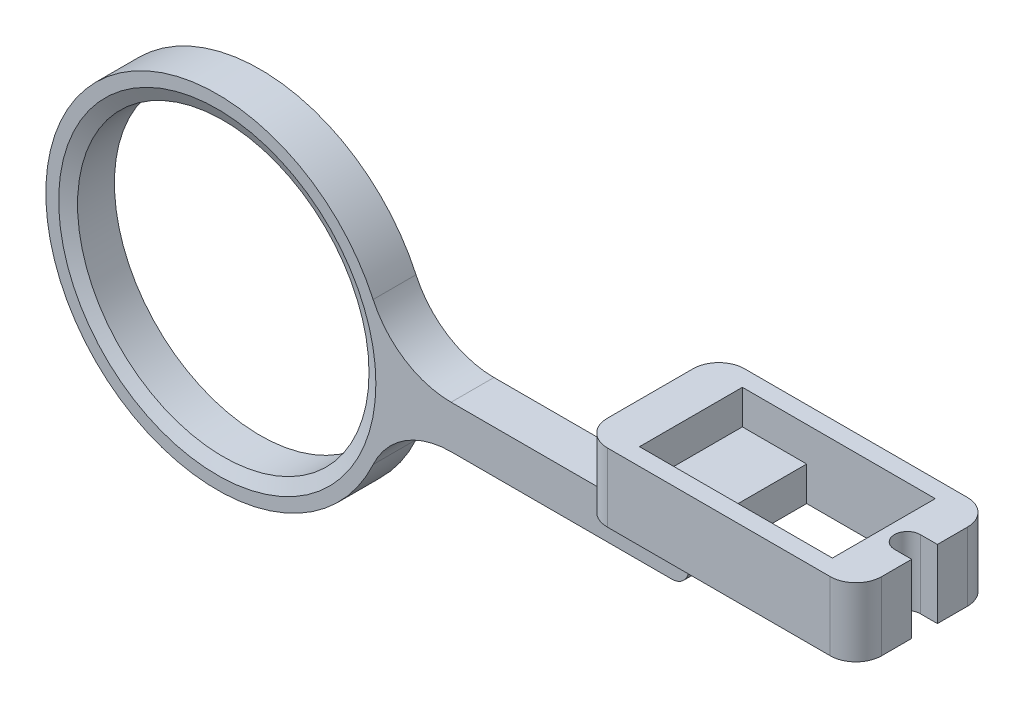
SolidWorks part; units mm, degrees
ref_plane "Plan de face" through (0, 0, 0) normal (0, 0, 1) x (1, 0, 0)
ref_plane "Plan de dessus" through (0, 0, 0) normal (0, 1, 0) x (1, 0, 0)
ref_plane "Plan de droite" through (0, 0, 0) normal (1, 0, 0) x (0, 0, -1)
sketch "Sketch1" plane through (0, 0, 0) normal (0, 0, 1) x (1, 0, 0)
  line L1 (0, 2.5) -> (80, 2.5)
  line L2 (0, 2.5) -> (0, -2.5)
  line L3 (0, -2.5) -> (80, -2.5)
  line L4 (80, 2.5) -> (80, -2.5)
  circle A0 centre (0, 0) radius 20
  circle A1 centre (0, 0) radius 17
  point P9 (0, 0)
  dimension "D1" = 40
  dimension "D3" = 80
  dimension "D4" = 5
  dimension "D2" = 3
extrude "Boss-Extrude1" add sketch "Sketch1" along normal blind 5 contours A1 L1 A0 L3 | A1 L3 A0 L1 | A0 L3 L4 L1 region at (-17.5646, 0, 0) region at (18.443, 0, 0) region at (49.9739, 0, 0)
chamfer "Chamfer2" distance 1.5 angle 25 1 edges at (17, 0, 5) first distance on face at (39.9608, 0, 5)
fillet "Fillet1" radius 10 2 edges at (19.8431, -2.5, 2.5) (19.8431, 2.5, 2.5)
sketch "Sketch4" plane through (0, 0, 0) normal (0, 1, 0) x (1, 0, 0)
  line L0 (18.5, -5) -> (17, -4.3005) construction
  circle A0 centre (0.2012, -29.5685) radius 30 construction
  dimension "D1" = 60
sketch "Sketch10" plane through (0, 2.5, 0) normal (0, 1, 0) x (1, 0, 0)
  line L0 (27.2718, 0) -> (80, 0) construction
  line L1 (80, -5) -> (48, -5)
  line L2 (80, -5) -> (80, 0)
  line L3 (80, 0) -> (48, 0)
  line L4 (48, -5) -> (48, 0)
  dimension "D1" = 32
extrude "Boss-Extrude3" add sketch "Sketch10" along normal blind 2
sketch "Sketch5" plane through (0, 4.5, 0) normal (0, 1, 0) x (1, 0, 0)
  line L0 (80, -5) -> (80, 0) construction
  line L1 (80, -10.5) -> (48, -10.5)
  line L2 (80, -10.5) -> (80, 5.5)
  line L3 (80, 5.5) -> (48, 5.5)
  line L4 (48, -10.5) -> (48, 5.5)
  point P7 (80, -2.5)
  point P8 (80, -2.5)
  dimension "D1" = 16
  dimension "D2" = 32
extrude "Boss-Extrude2" add sketch "Sketch5" along normal blind 8
sketch "Sketch6" plane through (0, 12.5, 0) normal (0, 1, 0) x (1, 0, 0)
  line L0 (80, 5.5) -> (48, 5.5) construction
  line L1 (52.75, 3.5) -> (75.25, 3.5)
  line L2 (52.75, 3.5) -> (52.75, -8.5)
  line L3 (52.75, -8.5) -> (75.25, -8.5)
  line L4 (75.25, 3.5) -> (75.25, -8.5)
  line L5 (80, -10.5) -> (80, 5.5) construction
  point P6 (64, 5.5)
  point P7 (64, 3.5)
  point P10 (80, -2.5)
  point P11 (75.25, -2.5)
  dimension "D1" = 12
  dimension "D2" = 22.5
extrude "Cut-Extrude1" cut sketch "Sketch6" against normal blind 4
sketch "Sketch7" plane through (0, -2.5, 0) normal (0, -1, 0) x (1, 0, 0)
  line L0 (27.2718, 0) -> (80, 0) construction
  line L1 (80, 5) -> (55, 5)
  line L2 (80, 5) -> (80, 0)
  line L3 (80, 0) -> (55, 0)
  line L4 (55, 5) -> (55, 0)
  dimension "D1" = 25
extrude "Cut-Extrude2" cut sketch "Sketch7" against normal up to surface (7 mm away) up to face at (64, 4.5, -2.75)
sketch "Sketch8" plane through (0, 8.5, 0) normal (0, 1, 0) x (1, 0, 0)
  line L0 (52.75, -8.5) -> (75.25, -8.5) construction
  line L1 (75.25, 3.5) -> (60.25, 3.5)
  line L2 (75.25, 3.5) -> (75.25, -8.5)
  line L3 (75.25, -8.5) -> (60.25, -8.5)
  line L4 (60.25, 3.5) -> (60.25, -8.5)
  dimension "D1" = 15
extrude "Cut-Extrude3" cut sketch "Sketch8" against normal through all
sketch "Sketch9" plane through (0, 4.5, 0) normal (0, -1, 0) x (1, 0, 0)
  line L0 (80, 10.5) -> (80, -5.5) construction
  line L3 (78, 4) -> (80, 4)
  line L4 (80, 4) -> (80, 1)
  line L5 (80, 1) -> (78, 1)
  arc A0 (78, 4) -> (78, 1) centre (78, 2.5) ccw
  point P6 (80, 2.5)
  dimension "D1" = 3
  dimension "D2" = 2
extrude "Cut-Extrude4" cut sketch "Sketch9" against normal through all
fillet "Fillet2" radius 2 3 edges at (55, 4.5, 2.5) (48, 2.5, 2.5) (55, -2.5, 2.5)
fillet "Fillet3" radius 1.5 2 edges at (52.5, 4.5, 5) (52.5, 4.5, 0)
fillet "Fillet4" radius 3 4 edges at (80, 8.5, 10.5) (48, 8.5, 10.5) (48, 8.5, -5.5) (80, 8.5, -5.5)
